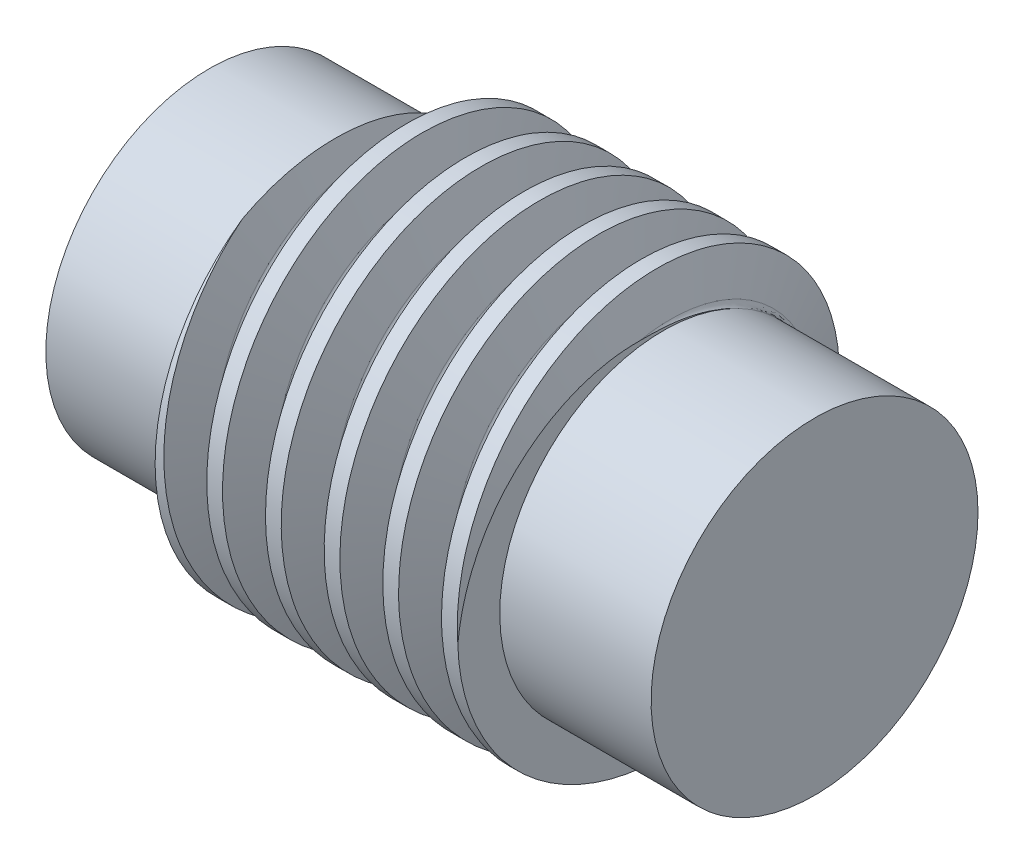
SolidWorks part; units mm, degrees
note: '?' marks a value the reader was unsure of.
ref_plane "前视基准面" through (0, 0, 0) normal (0, 0, 1) x (1, 0, 0)
ref_plane "上视基准面" through (0, 0, 0) normal (0, 1, 0) x (1, 0, 0)
ref_plane "右视基准面" through (0, 0, 0) normal (1, 0, 0) x (0, 0, -1)
ref_axis "基准轴1" through (-10.9638, 0, 0) along (1, 0, 0)?
sketch "草图1" plane through (0, 0, 0) normal (0, 0, 1) x (1, 0, 0)
  line L0 (-56.8494, 0) -> (118.6822, 0) construction
  line L1 (0, 48.1623) -> (0, -71.9241) construction
  line L2 (0, 11) -> (0, 0)
  line L3 (-10.9638, 0) -> (40.5935, 0) construction
  line L7 (0, 11) -> (16.2, 11)
  line L13 (0, 0) -> (16.2, 0)
  line L14 (16.2, 0) -> (16.2, 11)
  dimension "da1" = 11
  dimension "B1" = 16.2
revolve "旋转1" add sketch "草图1" angle 360 about L0
sketch "草图2" plane through (0, 0, 0) normal (1, 0, 0) x (0, 0, -1)
  circle A0 centre (0, 0) radius 10
  dimension "d1" = 20
sketch "草图3" plane through (0, 0, 0) normal (0, 0, 1) x (1, 0, 0)
  line L0 (0, 25.9401) -> (0, 0) construction
  line L1 (-3.4481, 11) -> (-1.1494, 11)
  line L2 (0, 11) -> (16.2, 11) construction
  line L3 (-1.1494, 11) -> (-1.8773, 9)
  line L4 (-2.2344, 8.75) -> (-2.3631, 8.75)
  line L5 (-2.2987, 11) -> (-2.2987, 8.75) construction
  line L6 (0, 0) -> (8.7963, 0) construction
  line L7 (-3.0841, 10) -> (-1.5133, 10) construction
  line L8 (-2.7202, 9) -> (-3.4481, 11)
  line L9 (-3.4481, 11) -> (-3.4481, -9) construction
  line L10 (-2.2987, 11) -> (0, 11) construction
  arc A0 (-2.7202, 9) -> (-2.3631, 8.75) centre (-2.3631, 9.13) ccw
  arc A1 (-2.2344, 8.75) -> (-1.8773, 9) centre (-2.2344, 9.13) ccw
  point P14 (-2.6292, 8.75)
  point P19 (-1.9683, 8.75)
  dimension "ppn" = 0.38
  dimension "df1" = 17.5
  dimension "d1" = 20
  dimension "0.5px" = 1.5708
  dimension "aa1" = 20
  dimension "aa" = 20
sketch "草图4" plane through (0, 0, 0) normal (1, 0, 0) x (0, 0, -1)
  circle A0 centre (0, 0) radius 8.75
sketch "草图5" plane through (16.2, 0, 0) normal (1, 0, 0) x (0, 0, -1)
  circle A0 centre (0, 0) radius 8.75 construction
  circle A1 centre (0, 0) radius 8.75
curve "螺旋线/涡状线1" pitch 3.1416 height 32.4 turns 10.3132
sweep "切除-扫描1" cut profiles "草图3" path "螺旋线/涡状线1"
extrude "凸台-拉伸1" add sketch "草图4" against normal blind 8.1
extrude "凸台-拉伸2" add sketch "草图5" along normal blind 8.1
